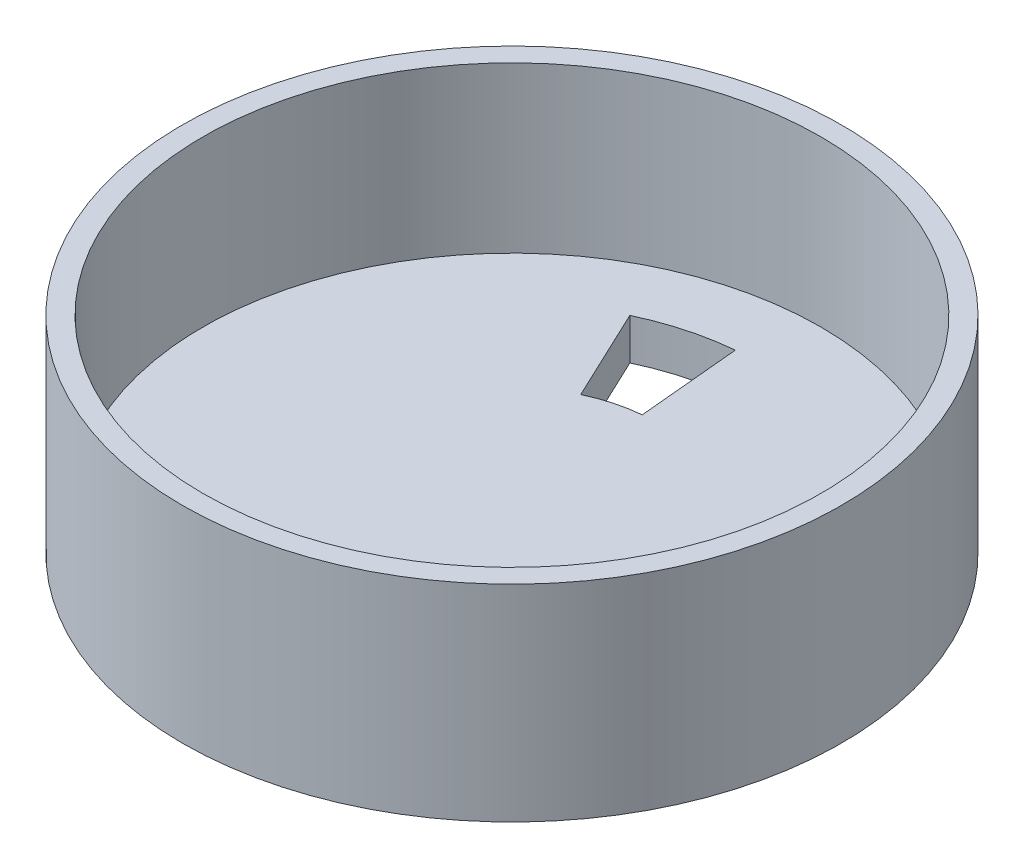
SolidWorks part; units mm, degrees
ref_plane "Front Plane" through (0, 0, 0) normal (0, 0, 1) x (1, 0, 0)
ref_plane "Top Plane" through (0, 0, 0) normal (0, 1, 0) x (1, 0, 0)
ref_plane "Right Plane" through (0, 0, 0) normal (1, 0, 0) x (0, 0, -1)
sketch "Sketch1" plane through (0, 0, 0) normal (0, 1, 0) x (1, 0, 0)
  circle A0 centre (0, 0) radius 16
  dimension "D1" = 32
extrude "Boss-Extrude1" add sketch "Sketch1" along normal blind 10
sketch "Sketch2" plane through (0, 10, 0) normal (0, 1, 0) x (1, 0, 0)
  circle A0 centre (0, 0) radius 15
  dimension "D1" = 30
extrude "Cut-Extrude1" cut sketch "Sketch2" against normal blind 8
sketch "Sketch3" plane through (0, 2, 0) normal (0, 1, 0) x (1, 0, 0)
  line L2 (-5.1256, 10.8503) -> (-2.9899, 6.3293)
  line L3 (-1.1055, 11.949) -> (-0.6449, 6.9702)
  line L4 (5.1256, -10.8503) -> (2.9899, -6.3293)
  line L5 (1.1055, -11.949) -> (0.6449, -6.9702)
  arc A0 (-1.1055, 11.949) -> (-5.1256, 10.8503) centre (0, 0) ccw
  arc A1 (-0.6449, 6.9702) -> (-2.9899, 6.3293) centre (0, 0) ccw
  arc A2 (1.1055, -11.949) -> (5.1256, -10.8503) centre (0, 0) ccw
  arc A3 (0.6449, -6.9702) -> (2.9899, -6.3293) centre (0, 0) ccw
  dimension "D1" = 2
  dimension "D2" = 5
  dimension "D3" = 7
extrude "Cut-Extrude2" cut sketch "Sketch3" against normal blind 8
